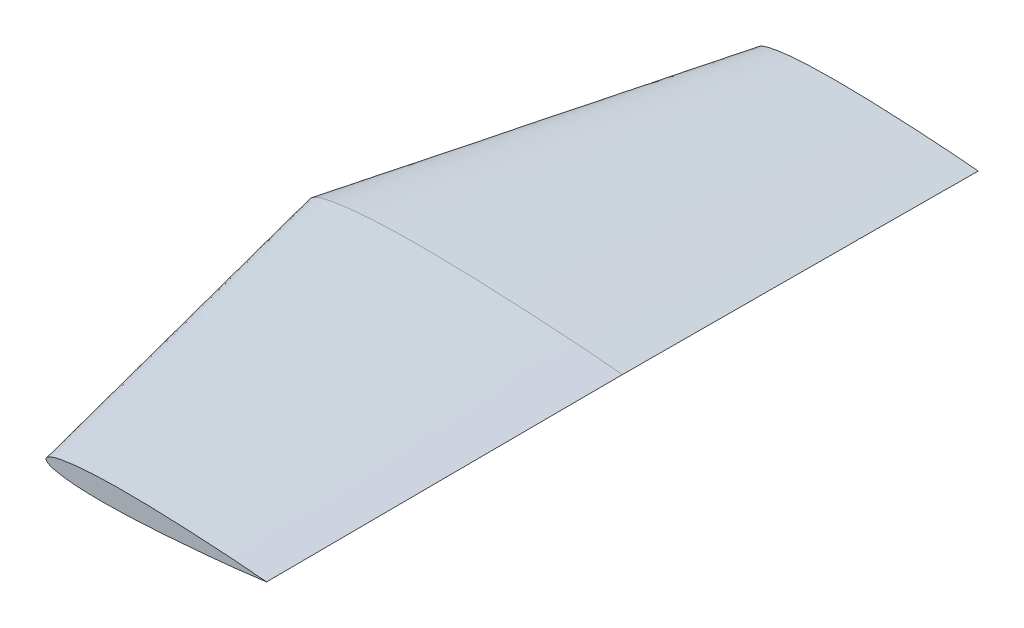
SolidWorks part; units mm, degrees
ref_plane "Front Plane" through (0, 0, 0) normal (0, 0, 1) x (1, 0, 0)
ref_plane "Top Plane" through (0, 0, 0) normal (0, 1, 0) x (1, 0, 0)
ref_plane "Right Plane" through (0, 0, 0) normal (1, 0, 0) x (0, 0, -1)
curve "Curve1"
  spline degree 3 poles (211.411, -0.2029, 0) (213.8499, 0, 0) (211.411, 0.2029, 0) (209.4121, 0.5413, 0) (204.5567, 1.0601, 0) (198.591, 1.7041, 0) (190.8179, 2.4598, 0) (181.6918, 3.2938, 0) (171.2526, 4.19, 0) (159.7189, 5.122, 0) (147.2745, 6.0528, 0) (134.1363, 6.9547, 0) (120.5284, 7.7863, 0) (106.6835, 8.5122, 0) (92.8382, 9.0894, 0) (81.4061, 9.4229, 0) (72.4382, 9.5761, 0) (65.9141, 9.6304, 0) (59.5642, 9.6228, 0) (53.4155, 9.5411, 0) (47.4948, 9.3976, 0) (41.8281, 9.1809, 0) (36.4392, 8.8989, 0) (31.3503, 8.545, 0) (26.5832, 8.1252, 0) (22.1596, 7.6358, 0) (18.0982, 7.0862, 0) (14.4147, 6.4905, 0) (11.1244, 5.8514, 0) (8.2382, 5.1711, 0) (5.7696, 4.4266, 0) (3.7241, 3.6043, 0) (2.1202, 2.697, 0) (0.9669, 1.7496, 0) (0.2466, 0.8812, 0) (-0.1009, 0, 0) (0.2466, -0.8812, 0) (0.9669, -1.7496, 0) (2.1202, -2.697, 0) (3.7241, -3.6043, 0) (5.7696, -4.4266, 0) (8.2382, -5.1711, 0) (11.1244, -5.8514, 0) (14.4147, -6.4905, 0) (18.0982, -7.0862, 0) (22.1596, -7.6358, 0) (26.5832, -8.1252, 0) (31.3503, -8.545, 0) (36.4392, -8.8989, 0) (41.8281, -9.1809, 0) (47.4948, -9.3976, 0) (53.4155, -9.5411, 0) (59.5642, -9.6228, 0) (65.9141, -9.6304, 0) (72.4382, -9.5761, 0) (81.4061, -9.4229, 0) (92.8382, -9.0894, 0) (106.6835, -8.5122, 0) (120.5284, -7.7863, 0) (134.1363, -6.9547, 0) (147.2745, -6.0528, 0) (159.7189, -5.122, 0) (171.2526, -4.19, 0) (181.6918, -3.2938, 0) (190.8179, -2.4598, 0) (198.591, -1.7041, 0) (204.5567, -1.0601, 0) (209.4121, -0.5413, 0) (211.411, -0.2029, 0) (213.8499, 0, 0) (211.411, 0.2029, 0) knots -0.018944 -0.008488 -0.002133 0 0.002133 0.008488 0.018944 0.033319 0.051356 0.072756 0.097141 0.124097 0.153163 0.183834 0.215589 0.247878 0.280151 0.31186 0.327333 0.342463 0.357187 0.371448 0.385183 0.398331 0.410845 0.422673 0.433769 0.44409 0.453589 0.46224 0.47001 0.476871 0.482833 0.487909 0.492155 0.495592 0.498196 0.5 0.501804 0.504408 0.507845 0.512091 0.517167 0.523129 0.52999 0.53776 0.546411 0.55591 0.566231 0.577327 0.589155 0.601669 0.614817 0.628552 0.642813 0.657537 0.672667 0.68814 0.719849 0.752122 0.784411 0.816166 0.846837 0.875903 0.902859 0.927244 0.948644 0.966681 0.981056 0.991512 0.997867 1 1.002133 1.008488 1.018944 periodic
sketch "Sketch1" plane through (0, 0, 0) normal (0, 0, 1) x (1, 0, 0)
  line L0 (0, 0) -> (223.486, 3.901) construction
  line L1 (0, 0) -> (0.3169, -18.1537) construction
  line L2 (0, 0) -> (107.4725, 0) construction
  spline S1 degree 3 poles (221.4482, 3.6528) (223.9991, 3.9099) (221.4408, 4.0779) (219.3408, 4.3958) (214.2454, 4.8505) (207.9849, 5.4159) (199.829, 6.0654) (190.2545, 6.7721) (179.3036, 7.5199) (167.2054, 8.2853) (154.1534, 9.0328) (140.3752, 9.7373) (126.1062, 10.3595) (111.591, 10.8668) (97.0781, 11.2182) (85.0973, 11.3585) (75.701, 11.355) (68.8663, 11.2926) (62.2151, 11.1686) (55.7761, 10.9705) (49.5771, 10.712) (43.6454, 10.3814) (38.0059, 9.9875) (32.682, 9.5238) (27.6962, 8.9969) (23.0717, 8.4034) (18.8275, 7.7534) (14.9801, 7.0621) (11.5454, 6.3325) (8.5347, 5.5671) (5.9625, 4.7422) (3.8349, 3.8435) (2.1716, 2.8638) (0.9808, 1.8503) (0.2422, 0.9275) (-0.1057, -0.0018) (0.2744, -0.9185) (1.0448, -1.8149) (2.2702, -2.7862) (3.9667, -3.7073) (6.1244, -4.5312) (8.7237, -5.2659) (11.7594, -5.9257) (15.2174, -6.535) (19.0866, -7.0916) (23.3509, -7.5931) (27.9933, -8.0248) (32.9944, -8.3774) (38.3313, -8.655) (43.9811, -8.8519) (49.9207, -8.9752) (56.125, -9.0173) (62.567, -8.9905) (69.2185, -8.8823) (76.0512, -8.7061) (85.4418, -8.3817) (97.4104, -7.8234) (111.9023, -6.9657) (126.3909, -5.9521) (140.6295, -4.8323) (154.3747, -3.6474) (167.3927, -2.4449) (179.4568, -1.2577) (190.375, -0.1282) (199.919, 0.9122) (208.0472, 1.8459) (214.2842, 2.6295) (219.3606, 3.2617) (221.4482, 3.6528) (223.9991, 3.9099) (221.4408, 4.0779) knots -0.018944 -0.008488 -0.002133 0 0.002133 0.008488 0.018944 0.033319 0.051356 0.072756 0.097141 0.124097 0.153163 0.183834 0.215589 0.247878 0.280151 0.31186 0.327333 0.342463 0.357187 0.371448 0.385183 0.398331 0.410845 0.422673 0.433769 0.44409 0.453589 0.46224 0.47001 0.476871 0.482833 0.487909 0.492155 0.495592 0.498196 0.5 0.501804 0.504408 0.507845 0.512091 0.517167 0.523129 0.52999 0.53776 0.546411 0.55591 0.566231 0.577327 0.589155 0.601669 0.614817 0.628552 0.642813 0.657537 0.672667 0.68814 0.719849 0.752122 0.784411 0.816166 0.846837 0.875903 0.902859 0.927244 0.948644 0.966681 0.981056 0.991512 0.997867 1 1.002133 1.008488 1.018944 only from (223.486, 3.901) to (223.486, 3.901)
  dimension "D1" = 223.52
  dimension "D2" = 1
ref_plane "Plane1" through (0, 0, 254) normal (0, 0, 1) x (1, 0, 0)
sketch "Sketch2" plane through (0, 0, 254) normal (0, 0, 1) x (1, 0, 0)
  line L0 (66.04, 0) -> (223.496, 2.7484) construction
  line L1 (66.04, 0) -> (67.3215, -73.4196) construction
  line L2 (66.04, 0) -> (152.4564, 0) construction
  spline S0 degree 3 poles (222.0603, 2.5735) (223.8575, 2.7547) (222.0551, 2.8731) (220.5756, 3.0971) (216.9856, 3.4174) (212.5748, 3.8158) (206.8286, 4.2734) (200.083, 4.7713) (192.3675, 5.2981) (183.8438, 5.8374) (174.6481, 6.364) (164.9407, 6.8604) (154.8876, 7.2987) (144.6609, 7.6561) (134.4359, 7.9038) (125.9949, 8.0026) (119.3748, 8.0001) (114.5594, 7.9562) (109.8734, 7.8688) (105.3368, 7.7292) (100.9693, 7.5471) (96.7902, 7.3142) (92.8169, 7.0366) (89.0659, 6.7099) (85.5532, 6.3387) (82.2951, 5.9206) (79.3048, 5.4626) (76.5942, 4.9756) (74.1743, 4.4615) (72.0531, 3.9223) (70.2409, 3.3411) (68.7419, 2.7079) (67.57, 2.0177) (66.731, 1.3036) (66.2106, 0.6535) (65.9655, -0.0013) (66.2333, -0.6471) (66.7761, -1.2787) (67.6394, -1.963) (68.8347, -2.612) (70.3549, -3.1925) (72.1863, -3.71) (74.325, -4.1749) (76.7614, -4.6042) (79.4874, -4.9964) (82.4918, -5.3497) (85.7626, -5.6538) (89.2861, -5.9022) (93.0461, -6.0979) (97.0267, -6.2366) (101.2114, -6.3235) (105.5826, -6.3531) (110.1213, -6.3342) (114.8076, -6.258) (119.6215, -6.1339) (126.2377, -5.9053) (134.6701, -5.512) (144.8802, -4.9076) (155.0882, -4.1935) (165.1199, -3.4046) (174.804, -2.5698) (183.9758, -1.7226) (192.4755, -0.8861) (200.1678, -0.0903) (206.892, 0.6427) (212.6187, 1.3005) (217.013, 1.8526) (220.5895, 2.2981) (222.0603, 2.5735) (223.8575, 2.7547) (222.0551, 2.8731) knots -0.018944 -0.008488 -0.002133 0 0.002133 0.008488 0.018944 0.033319 0.051356 0.072756 0.097141 0.124097 0.153163 0.183834 0.215589 0.247878 0.280151 0.31186 0.327333 0.342463 0.357187 0.371448 0.385183 0.398331 0.410845 0.422673 0.433769 0.44409 0.453589 0.46224 0.47001 0.476871 0.482833 0.487909 0.492155 0.495592 0.498196 0.5 0.501804 0.504408 0.507845 0.512091 0.517167 0.523129 0.52999 0.53776 0.546411 0.55591 0.566231 0.577327 0.589155 0.601669 0.614817 0.628552 0.642813 0.657537 0.672667 0.68814 0.719849 0.752122 0.784411 0.816166 0.846837 0.875903 0.902859 0.927244 0.948644 0.966681 0.981056 0.991512 0.997867 1 1.002133 1.008488 1.018944 only from (223.496, 2.7484) to (223.496, 2.7484)
  dimension "D1" = 157.48
  dimension "D2" = 1
  dimension "D3" = 66.04
loft "Loft1" add profiles "Sketch1", "Sketch2" connector at (0.0116, 0.1783, 0) connector at (66.0651, -0.184, 254)
mirror "Mirror1" about plane through (0, 0, 0) normal (0, 0, -1) of "Loft1"
